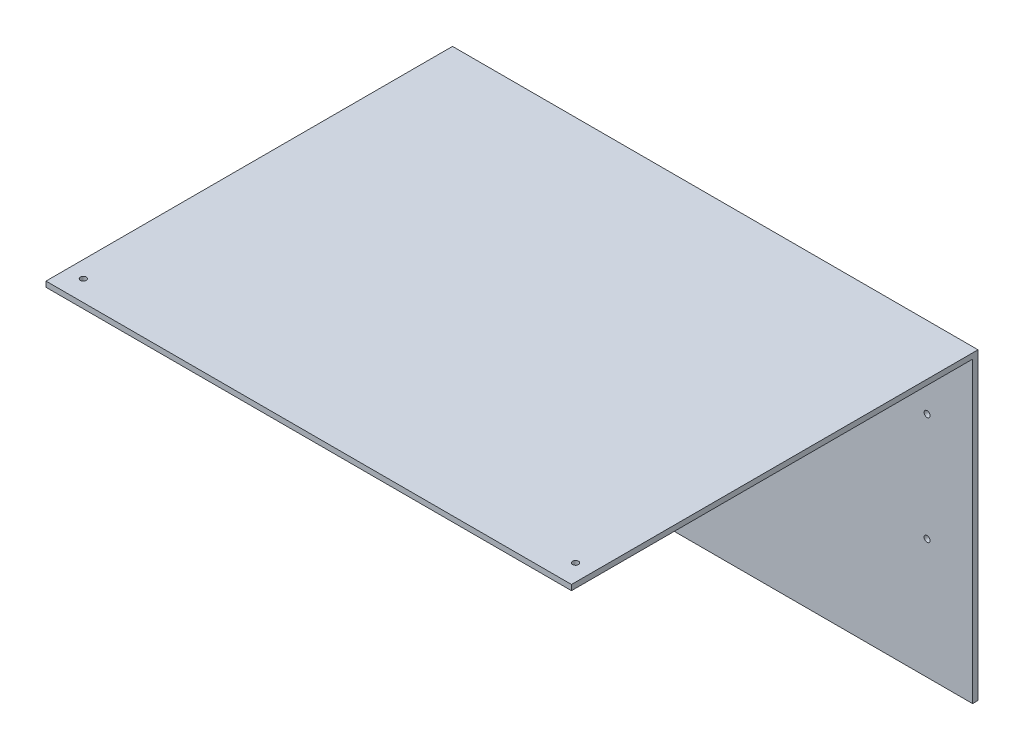
SolidWorks part; units mm, degrees
ref_plane "Front Plane" through (0, 0, 0) normal (0, 0, 1) x (1, 0, 0)
ref_plane "Top Plane" through (0, 0, 0) normal (0, 1, 0) x (1, 0, 0)
ref_plane "Right Plane" through (0, 0, 0) normal (1, 0, 0) x (0, 0, -1)
sketch "Sketch1" plane through (0, 0, 0) normal (0, 0, 1) x (1, 0, 0)
  line L1 (0, 0) -> (291.5, 0)
  line L2 (0, 0) -> (0, -168.5)
  line L3 (0, -168.5) -> (291.5, -168.5)
  line L4 (291.5, 0) -> (291.5, -168.5)
  dimension "D1" = 291.5
  dimension "D2" = 168.5
extrude "Boss-Extrude1" add sketch "Sketch1" along normal blind 3
sketch "Sketch2" plane through (0, 0, 3) normal (0, 0, 1) x (1, 0, 0)
  line L0 (145.75, 0) -> (145.75, -168.5) construction
  line L1 (291.5, 0) -> (0, 0) construction
  line L2 (0, -168.5) -> (291.5, -168.5) construction
  point P6 (25.25, -42)
  point P7 (25.25, -102)
  point P8 (0, 0)
  point P9 (0, 0)
  point P10 (0, 0)
  point P11 (266.25, -102)
  point P12 (266.25, -42)
  dimension "D1" = 120.5
  dimension "D2" = 42
  dimension "D3" = 60
hole_wizard "Tap Drill for M4 Tap1" positions "Sketch3" profile "Sketch4" hole size "M4" standard "ISO" end condition up to next
sketch "Sketch3" plane through (0, 0, 3) normal (0, 0, 1) x (1, 0, 0)
  point P0 (25.25, -102)
  point P3 (25.25, -42)
  point P6 (266.25, -42)
  point P9 (266.25, -102)
sketch "Sketch4" plane through (25.25, -102, 3) normal (1, 0, 0) x (0, -1, 0)
  line L0 (0, 0) -> (0, 3)
  line L1 (0, 3) -> (1.65, 3)
  line L2 (1.65, 3) -> (1.65, 0)
  line L5 (1.65, 0) -> (0, 0)
  line L11 (0, -6.35) -> (0, 107.95) construction
  dimension "Thru Hole Dia." = 3.3
  dimension "Thru Hole Depth" = 3
sketch "Sketch6" plane through (0, 0, 3) normal (0, 0, 1) x (1, 0, 0)
  line L0 (291.5, -168.5) -> (291.5, 0) construction
  line L1 (0, 0) -> (291.5, 0)
  line L2 (0, 0) -> (0, -3)
  line L3 (0, -3) -> (291.5, -3)
  line L4 (291.5, 0) -> (291.5, -3)
  dimension "D1" = 3
extrude "Boss-Extrude2" add sketch "Sketch6" along normal blind 222.5
sketch "Sketch7" plane through (0, 0, 0) normal (0, 1, 0) x (1, 0, 0)
  line L0 (145.75, 0) -> (145.75, -225.5) construction
  line L1 (291.5, 0) -> (0, 0) construction
  line L2 (291.5, -225.5) -> (0, -225.5) construction
  point P0 (9.25, -214)
  point P7 (282.25, -214)
  dimension "D1" = 136.5
  dimension "D2" = 11.5
hole_wizard "Tap Drill for M4 Tap2" positions "Sketch7" profile "Sketch8" hole size "M4" standard "ISO" end condition up to next
sketch "Sketch8" plane through (9.25, 0, 214) normal (1, 0, 0) x (0, 0, 1)
  line L0 (0, 0) -> (0, 3)
  line L1 (0, 3) -> (1.65, 3)
  line L2 (1.65, 3) -> (1.65, 0)
  line L5 (1.65, 0) -> (0, 0)
  line L11 (0, -6.35) -> (0, 107.95) construction
  dimension "Thru Hole Dia." = 3.3
  dimension "Thru Hole Depth" = 3
